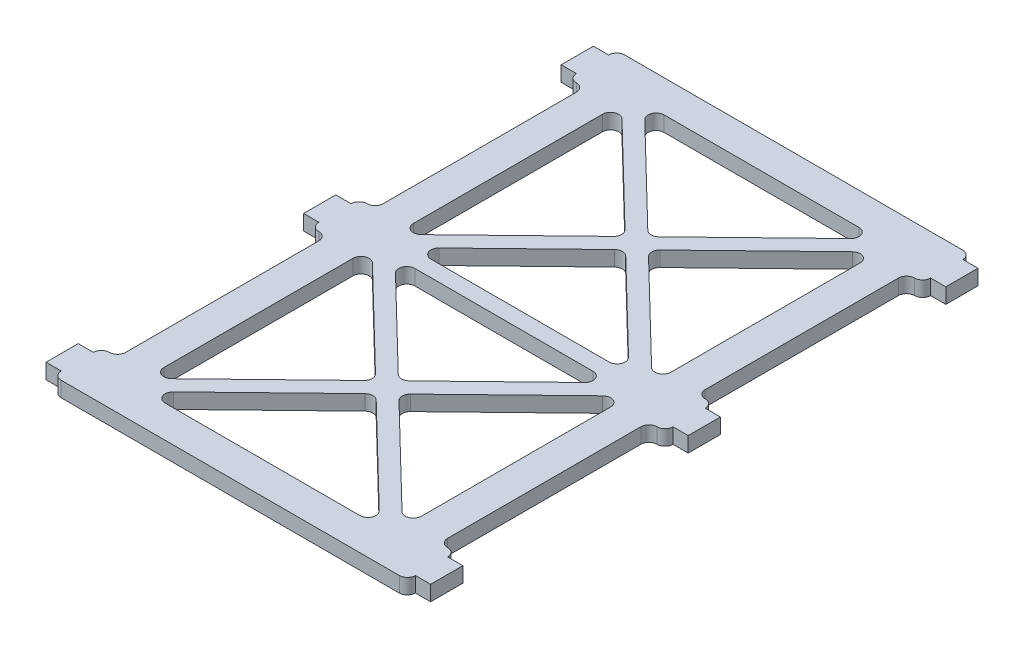
SolidWorks part; units mm, degrees
ref_plane "Front Plane" through (0, 0, 0) normal (0, 0, 1) x (1, 0, 0)
ref_plane "Top Plane" through (0, 0, 0) normal (0, 1, 0) x (1, 0, 0)
ref_plane "Right Plane" through (0, 0, 0) normal (1, 0, 0) x (0, 0, -1)
sketch "Sketch1" plane through (0, 34.29, 0) normal (0, 1, 0) x (1, 0, 0)
  line L0 (35.1028, 190.5) -> (38.1, 190.5) construction
  line L1 (0, -190.5) -> (0, 187.198) construction
  line L2 (38.1028, 187.198) -> (35.1028, 187.198) construction
  line L3 (35.1028, -190.5) -> (38.1, -190.5) construction
  line L5 (-31.75, 65.0875) -> (31.75, 65.0875)
  line L6 (-31.75, 65.0875) -> (-31.75, 176.2125)
  line L7 (-31.75, 176.2125) -> (31.75, 176.2125)
  line L8 (31.75, 65.0875) -> (31.75, 176.2125)
  line L9 (-31.75, 65.0875) -> (31.75, 176.2125) construction
  line L10 (-31.75, 176.2125) -> (31.75, 65.0875) construction
  point P0 (0, 120.65)
  dimension "D1" = 111.125
  dimension "D2" = 63.5
  dimension "D3" = 14.2875
extrude "Boss-Extrude1" add sketch "Sketch1" along normal mid plane 3 contours L7 L8 L5 L6
sketch "Sketch2" plane through (0, 35.79, 0) normal (0, 1, 0) x (1, 0, 0)
  line L0 (0, 176.2125) -> (0, 65.0186) construction
  line L1 (-31.75, 176.2125) -> (31.75, 176.2125) construction
  line L2 (31.75, 120.65) -> (-31.75, 120.65) construction
  line L3 (31.75, 65.0875) -> (31.75, 176.2125) construction
  line L4 (-31.75, 65.0875) -> (-31.75, 176.2125) construction
  line L5 (-34.925, 176.2125) -> (-31.75, 166.6875) construction
  line L6 (34.925, 166.6875) -> (31.75, 166.6875)
  line L7 (34.925, 166.6875) -> (34.925, 176.2125)
  line L8 (34.925, 176.2125) -> (31.75, 176.2125)
  line L9 (31.75, 166.6875) -> (31.75, 176.2125)
  line L10 (34.925, 166.6875) -> (31.75, 176.2125) construction
  line L11 (34.925, 176.2125) -> (31.75, 166.6875) construction
  line L12 (-34.925, 166.6875) -> (-31.75, 176.2125) construction
  line L13 (-31.75, 166.6875) -> (-31.75, 176.2125)
  line L14 (-34.925, 176.2125) -> (-31.75, 176.2125)
  line L15 (-34.925, 166.6875) -> (-34.925, 176.2125)
  line L16 (-34.925, 166.6875) -> (-31.75, 166.6875)
  line L17 (34.925, 115.8875) -> (31.75, 115.8875)
  line L18 (34.925, 115.8875) -> (34.925, 125.4125)
  line L19 (34.925, 125.4125) -> (31.75, 125.4125)
  line L20 (31.75, 115.8875) -> (31.75, 125.4125)
  line L21 (34.925, 115.8875) -> (31.75, 125.4125) construction
  line L22 (34.925, 125.4125) -> (31.75, 115.8875) construction
  line L23 (-31.75, 115.8875) -> (-31.75, 125.4125)
  line L24 (-34.925, 125.4125) -> (-31.75, 125.4125)
  line L25 (-34.925, 115.8875) -> (-34.925, 125.4125)
  line L26 (-34.925, 115.8875) -> (-31.75, 115.8875)
  line L27 (-34.925, 125.4125) -> (-31.75, 115.8875) construction
  line L28 (-34.925, 115.8875) -> (-31.75, 125.4125) construction
  line L29 (34.925, 65.0875) -> (31.75, 65.0875)
  line L30 (34.925, 65.0875) -> (34.925, 74.6125)
  line L31 (34.925, 74.6125) -> (31.75, 74.6125)
  line L32 (31.75, 65.0875) -> (31.75, 74.6125)
  line L33 (34.925, 65.0875) -> (31.75, 74.6125) construction
  line L34 (34.925, 74.6125) -> (31.75, 65.0875) construction
  line L35 (-31.75, 65.0875) -> (-31.75, 74.6125)
  line L36 (-34.925, 74.6125) -> (-31.75, 74.6125)
  line L37 (-34.925, 65.0875) -> (-34.925, 74.6125)
  line L38 (-34.925, 65.0875) -> (-31.75, 65.0875)
  line L39 (-34.925, 74.6125) -> (-31.75, 65.0875) construction
  line L40 (-34.925, 65.0875) -> (-31.75, 74.6125) construction
  point P11 (33.3375, 171.45)
  point P21 (-33.3375, 171.45)
  point P24 (33.3375, 120.65)
  point P33 (-33.3375, 120.65)
  point P34 (33.3375, 69.85)
  point P43 (-33.3375, 69.85)
  dimension "D1" = 3.175
  dimension "D2" = 9.525
  dimension "D3" = 3
extrude "Boss-Extrude2" add sketch "Sketch2" against normal up to surface (3 mm away) up to face at (0, 32.79, -120.65)
sketch "Sketch4" plane through (0, 35.79, 0) normal (0, 1, 0) x (1, 0, 0)
  line L0 (31.75, 125.4125) -> (31.75, 166.6875) construction
  line L1 (-25.4, 169.8625) -> (25.4, 169.8625)
  line L2 (-25.4, 169.8625) -> (-25.4, 71.4375)
  line L3 (-25.4, 71.4375) -> (25.4, 71.4375)
  line L4 (25.4, 169.8625) -> (25.4, 71.4375)
  line L5 (-25.4, 169.8625) -> (25.4, 71.4375) construction
  line L6 (-25.4, 71.4375) -> (25.4, 169.8625) construction
  line L7 (-31.75, 125.4125) -> (-31.75, 166.6875) construction
  line L8 (-34.925, 176.2125) -> (34.925, 176.2125) construction
  line L9 (-34.925, 65.0875) -> (34.925, 65.0875) construction
  line L10 (-25.4, 120.65) -> (25.4, 120.65) construction
  line L11 (25.4, 120.65) -> (-25.4, 169.8625) construction
  line L12 (25.4, 120.65) -> (-25.4, 71.4375) construction
  line L13 (-25.4, 120.65) -> (25.4, 169.8625) construction
  line L14 (25.4, 71.4375) -> (-25.4, 120.65) construction
  line L15 (-25.4, 119.0625) -> (25.4, 119.0625)
  line L16 (-25.4, 122.2375) -> (25.4, 122.2375)
  line L17 (26.5046, 72.5777) -> (-23.1184, 120.65)
  line L18 (-23.1184, 120.65) -> (26.5046, 168.7223)
  line L19 (27.6816, 120.65) -> (-24.2954, 70.2973)
  line L20 (27.6816, 120.65) -> (-24.2954, 171.0027)
  line L21 (24.2954, 70.2973) -> (-27.6816, 120.65)
  line L22 (-27.6816, 120.65) -> (24.2954, 171.0027)
  line L23 (23.1184, 120.65) -> (-26.5046, 72.5777)
  line L24 (23.1184, 120.65) -> (-26.5046, 168.7223)
  point P0 (0, 120.65)
  dimension "D1" = 6.35
  dimension "D2" = 6.35
  dimension "D3" = 6.35
  dimension "D4" = 6.35
  dimension "D5" = 1.5875
  dimension "D6" = 1.5875
  dimension "D7" = 1.5875
  dimension "D8" = 1.5875
extrude "Cut-Extrude1" cut sketch "Sketch4" against normal blind 3 contours L15 L19 L17 L4 | L3 L21 L19 | L23 L21 L15 L2 | L23 L15 L17 | L16 L24 L18 | L20 L16 L4 L18 | L20 L22 L1 | L22 L24 L2 L16 region at (0, 35.79, -162.3972) region at (-17.6939, 35.79, -145.2563) region at (17.6939, 35.79, -145.2563) region at (0, 35.79, -129.1737) region at (-17.6939, 35.79, -96.0438) region at (0, 35.79, -112.1263) region at (17.6939, 35.79, -96.0438) region at (0, 35.79, -78.9028)
fillet "Fillet1" radius 1.5875 44 edges at (-21.4797, 34.29, -119.0625) (21.4797, 34.29, -119.0625) (0, 34.29, -98.254) (-25.4, 34.29, -118.4397) (-2.2816, 34.29, -96.0438) (-25.4, 34.29, -73.6478) (25.4, 34.29, -167.6522) (25.4, 34.29, -122.8603) (2.2816, 34.29, -145.2563) (23.1184, 34.29, -169.8625) (0, 34.29, -147.4665) (-23.1184, 34.29, -169.8625) (2.2816, 34.29, -96.0438) (25.4, 34.29, -118.4397) (25.4, 34.29, -73.6478) (34.925, 34.29, -65.0875) (34.925, 34.29, -74.6125) (31.75, 34.29, -74.6125) (31.75, 34.29, -115.8875) (34.925, 34.29, -115.8875) (34.925, 34.29, -125.4125) (31.75, 34.29, -125.4125) (31.75, 34.29, -166.6875) (34.925, 34.29, -166.6875) (34.925, 34.29, -176.2125) (-34.925, 34.29, -166.6875) (-31.75, 34.29, -166.6875) (-31.75, 34.29, -125.4125) (-34.925, 34.29, -125.4125) (-34.925, 34.29, -115.8875) (-31.75, 34.29, -115.8875) (-31.75, 34.29, -74.6125) (-34.925, 34.29, -74.6125) (-34.925, 34.29, -65.0875) (-25.4, 34.29, -122.8603) (-25.4, 34.29, -167.6522) (-2.2816, 34.29, -145.2563) (-23.1184, 34.29, -71.4375) (0, 34.29, -93.8335) (23.1184, 34.29, -71.4375) (-21.4797, 34.29, -122.2375) (0, 34.29, -143.046) (21.4797, 34.29, -122.2375) (-34.925, 34.29, -176.2125)
sketch "Sketch5" plane through (0, 35.79, 0) normal (0, 1, 0) x (1, 0, 0)
  line L0 (34.925, 168.275) -> (34.925, 174.625) construction
  line L1 (37.925, 168.275) -> (34.925, 168.275)
  line L2 (37.925, 168.275) -> (37.925, 174.625)
  line L3 (37.925, 174.625) -> (34.925, 174.625)
  line L4 (34.925, 168.275) -> (34.925, 174.625)
  line L5 (37.925, 168.275) -> (34.925, 174.625) construction
  line L6 (37.925, 174.625) -> (34.925, 168.275) construction
  line L7 (34.925, 168.275) -> (34.925, 174.625) construction
  line L8 (34.925, 171.45) -> (36.425, 171.45) construction
  line L9 (0, 196.0278) -> (0, 0) construction
  line L10 (-34.925, 171.45) -> (-36.425, 171.45) construction
  line L11 (-37.925, 174.625) -> (-34.925, 168.275) construction
  line L12 (-37.925, 168.275) -> (-34.925, 174.625) construction
  line L13 (-34.925, 168.275) -> (-34.925, 174.625)
  line L14 (-37.925, 174.625) -> (-34.925, 174.625)
  line L15 (-37.925, 168.275) -> (-37.925, 174.625)
  line L16 (-37.925, 168.275) -> (-34.925, 168.275)
  line L17 (37.925, 117.475) -> (34.925, 117.475)
  line L18 (37.925, 117.475) -> (37.925, 123.825)
  line L19 (37.925, 123.825) -> (34.925, 123.825)
  line L20 (34.925, 117.475) -> (34.925, 123.825)
  line L21 (37.925, 117.475) -> (34.925, 123.825) construction
  line L22 (37.925, 123.825) -> (34.925, 117.475) construction
  line L23 (34.925, 120.65) -> (36.425, 120.65) construction
  line L24 (-34.925, 117.475) -> (-34.925, 123.825)
  line L25 (-37.925, 123.825) -> (-34.925, 123.825)
  line L26 (-37.925, 117.475) -> (-37.925, 123.825)
  line L27 (-37.925, 117.475) -> (-34.925, 117.475)
  line L28 (-34.925, 120.65) -> (-36.425, 120.65) construction
  line L29 (-37.925, 123.825) -> (-34.925, 117.475) construction
  line L30 (-37.925, 117.475) -> (-34.925, 123.825) construction
  line L31 (37.925, 66.675) -> (34.925, 66.675)
  line L32 (37.925, 66.675) -> (37.925, 73.025)
  line L33 (37.925, 73.025) -> (34.925, 73.025)
  line L34 (34.925, 66.675) -> (34.925, 73.025)
  line L35 (37.925, 66.675) -> (34.925, 73.025) construction
  line L36 (37.925, 73.025) -> (34.925, 66.675) construction
  line L37 (34.925, 69.85) -> (36.425, 69.85) construction
  line L38 (-34.925, 66.675) -> (-34.925, 73.025)
  line L39 (-37.925, 73.025) -> (-34.925, 73.025)
  line L40 (-37.925, 66.675) -> (-37.925, 73.025)
  line L41 (-37.925, 66.675) -> (-34.925, 66.675)
  line L42 (-34.925, 69.85) -> (-36.425, 69.85) construction
  line L43 (-37.925, 73.025) -> (-34.925, 66.675) construction
  line L44 (-37.925, 66.675) -> (-34.925, 73.025) construction
  line L45 (-36.425, 171.45) -> (-36.425, 120.65) construction
  point P0 (36.425, 171.45)
  point P7 (36.425, 120.65)
  point P21 (-36.425, 171.45)
  point P35 (-36.425, 120.65)
  point P36 (36.425, 69.85)
  point P49 (-36.425, 69.85)
  dimension "D1" = 3
  dimension "D2" = 6.35
  dimension "D4" = 50.8
  dimension "D3" = 3
extrude "Boss-Extrude3" add sketch "Sketch5" against normal up to surface (3 mm away) up to face at (0, 32.79, -129.6767)
